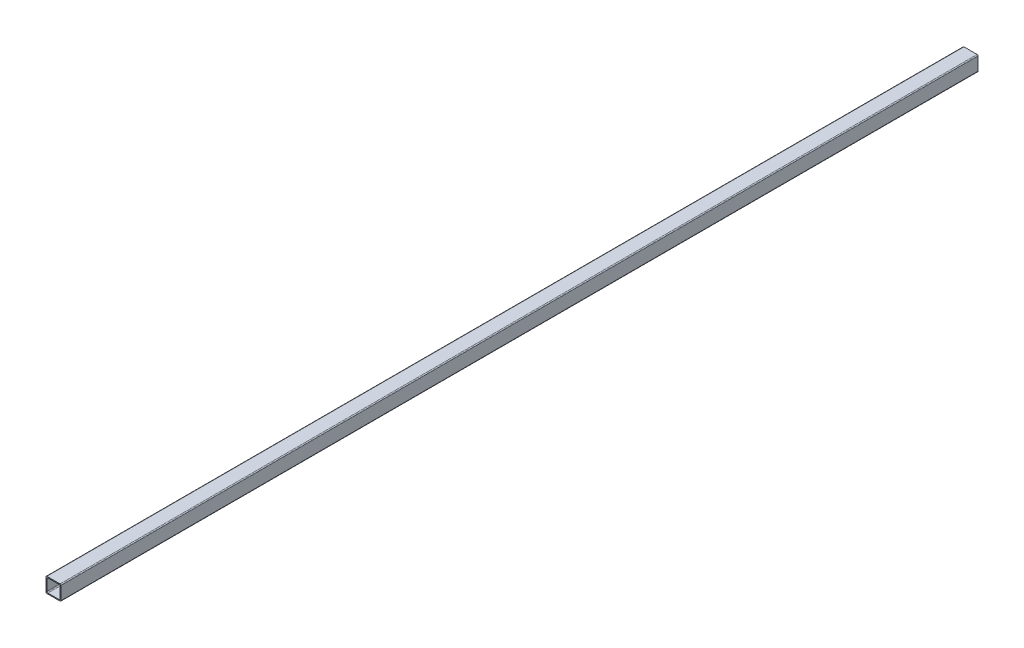
SolidWorks part; units mm, degrees
material "Hexcel AS4C (3000 Filaments)"
ref_plane "Front Plane" through (0, 0, 0) normal (0, 0, 1) x (1, 0, 0)
ref_plane "Top Plane" through (0, 0, 0) normal (0, 1, 0) x (1, 0, 0)
ref_plane "Right Plane" through (0, 0, 0) normal (1, 0, 0) x (0, 0, -1)
sketch "Sketch1" plane through (0, 0, 0) normal (0, 0, 1) x (1, 0, 0)
  line L1 (3.5, -3.5) -> (-3.5, -3.5)
  line L2 (3.5, -3.5) -> (3.5, 3.5)
  line L3 (3.5, 3.5) -> (-3.5, 3.5)
  line L4 (-3.5, -3.5) -> (-3.5, 3.5)
  line L5 (3.5, -3.5) -> (-3.5, 3.5) construction
  line L6 (3.5, 3.5) -> (-3.5, -3.5) construction
  line L7 (4, -4) -> (-4, -4)
  line L8 (4, -4) -> (4, 4)
  line L9 (4, 4) -> (-4, 4)
  line L10 (-4, -4) -> (-4, 4)
  line L11 (4, -4) -> (-4, 4) construction
  line L12 (4, 4) -> (-4, -4) construction
  point P0 (0, 0)
  point P6 (0, 0)
  dimension "D1" = 8
  dimension "D2" = 0.5
extrude "Boss-Extrude1" add sketch "Sketch1" along normal blind 490
fillet "Fillet1" radius 0.5 8 edges at (4, 4, 245) (3.5, 3.5, 245) (4, -4, 245) (3.5, -3.5, 245) (-3.5, -3.5, 245) (-4, -4, 245) (-4, 4, 245) (-3.5, 3.5, 245)
